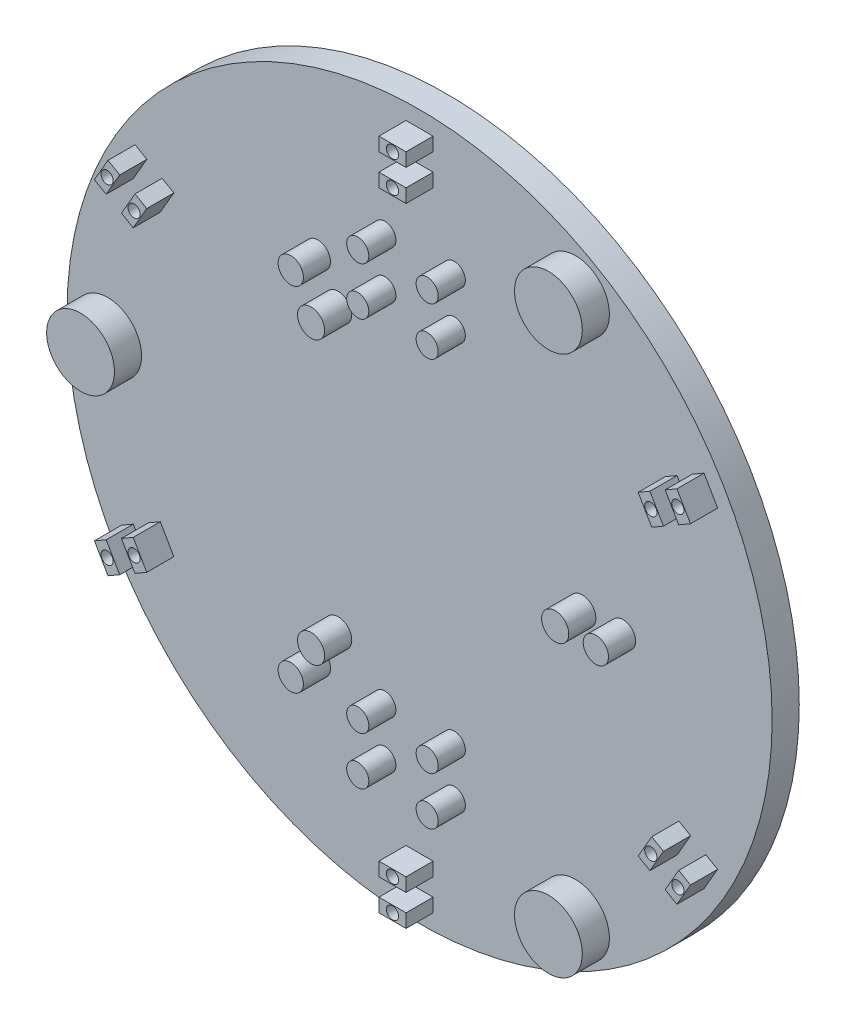
SolidWorks part; units mm, degrees
ref_plane "Front Plane" through (0, 0, 0) normal (0, 0, 1) x (1, 0, 0)
ref_plane "Top Plane" through (0, 0, 0) normal (0, 1, 0) x (1, 0, 0)
ref_plane "Right Plane" through (0, 0, 0) normal (1, 0, 0) x (0, 0, -1)
sketch "Sketch1" plane through (0, 0, 0) normal (0, 0, 1) x (1, 0, 0)
  circle A0 centre (0, 0) radius 33.02
  dimension "D1" = 66.04
extrude "Boss-Extrude1" add sketch "Sketch1" along normal blind 2.54
sketch "Sketch2" plane through (0, 0, 2.54) normal (0, 0, 1) x (1, 0, 0)
  line L0 (0, 33.02) -> (0, 0) construction
  line L1 (0, 0) -> (14.605, 25.2966) construction
  line L2 (14.605, 25.2966) -> (16.51, 28.5962) construction
  circle A1 centre (14.605, 25.2966) radius 3.175
  circle A2 centre (0, 0) radius 33.02 construction
  dimension "D1" = 6.35
  dimension "D2" = 3.81
  dimension "D3" = 30
extrude "Boss-Extrude2" add sketch "Sketch2" along normal blind 2.54
ref_axis "Axis1" through (0, 0, 34.6482) along (0, 0, -1)
pattern_circular "CirPattern1" count 3 over 360 about axis through (0, 0, 34.6482) along (0, 0, -1) of "Boss-Extrude2"
sketch "Sketch3" plane through (0, 0, 2.54) normal (0, 0, 1) x (1, 0, 0)
  line L0 (0, 0) -> (0, -27.94) construction
  line L1 (0, -27.94) -> (0, -33.02) construction
  line L3 (-1.27, -27.305) -> (1.27, -27.305)
  line L4 (-1.27, -27.305) -> (-1.27, -28.575)
  line L5 (-1.27, -28.575) -> (1.27, -28.575)
  line L6 (1.27, -27.305) -> (1.27, -28.575)
  line L7 (-1.27, -27.305) -> (1.27, -28.575) construction
  line L8 (-1.27, -28.575) -> (1.27, -27.305) construction
  line L16 (-1.27, -30.226) -> (1.27, -30.226)
  line L17 (-1.27, -30.226) -> (-1.27, -31.496)
  line L18 (-1.27, -31.496) -> (1.27, -31.496)
  line L19 (1.27, -30.226) -> (1.27, -31.496)
  line L20 (-1.27, -30.226) -> (1.27, -31.496) construction
  line L21 (-1.27, -31.496) -> (1.27, -30.226) construction
  circle A0 centre (0, 0) radius 33.02 construction
  circle A2 centre (0, -27.94) radius 0.5715
  circle A3 centre (0, -30.861) radius 0.5715
  point P10 (-3.81, -30.1721)
  point P11 (0, -30.48)
  point P12 (0, -30.48)
  point P13 (0.0188, -30.5629)
  dimension "D5" = 2.921
  dimension "D4" = 1.143
  dimension "D1" = 2.54
  dimension "D2" = 1.27
  dimension "D3" = 5.08
extrude "Boss-Extrude3" add sketch "Sketch3" along normal blind 2.54
pattern_circular "CirPattern8" count 6 over 360 about axis through (0, 0, 34.6482) along (0, 0, -1) of "Boss-Extrude3"
sketch "Sketch4" plane through (0, 0, 2.54) normal (0, 0, 1) x (1, 0, 0)
  line L0 (0, 0) -> (0, 19.05) construction
  line L1 (0, 0) -> (0, -19.05) construction
  line L2 (-3.2512, 21.2979) -> (3.2512, 21.2979) construction
  line L3 (-3.2512, 21.2979) -> (-3.2512, 16.8021) construction
  line L4 (-3.2512, 16.8021) -> (3.2512, 16.8021) construction
  line L5 (3.2512, 21.2979) -> (3.2512, 16.8021) construction
  line L6 (-3.2512, 21.2979) -> (3.2512, 16.8021) construction
  line L7 (-3.2512, 16.8021) -> (3.2512, 21.2979) construction
  line L9 (-3.2512, -16.8021) -> (3.2512, -16.8021) construction
  line L10 (-3.2512, -16.8021) -> (-3.2512, -21.2979) construction
  line L11 (-3.2512, -21.2979) -> (3.2512, -21.2979) construction
  line L12 (3.2512, -16.8021) -> (3.2512, -21.2979) construction
  line L13 (-3.2512, -16.8021) -> (3.2512, -21.2979) construction
  line L14 (-3.2512, -21.2979) -> (3.2512, -16.8021) construction
  circle A0 centre (-3.2512, 21.2979) radius 1.0363
  circle A1 centre (-3.2512, -16.8021) radius 1.0363
  circle A2 centre (3.2512, 21.2979) radius 1.0363
  circle A3 centre (3.2512, 16.8021) radius 1.0363
  circle A4 centre (-3.2512, 16.8021) radius 1.0363
  circle A5 centre (3.2512, -16.8021) radius 1.0363
  circle A6 centre (3.2512, -21.2979) radius 1.0363
  circle A7 centre (-3.2512, -21.2979) radius 1.0363
  dimension "D4" = 2.0726
  dimension "D1" = 4.4958
  dimension "D2" = 6.5024
  dimension "D3" = 19.05
extrude "Boss-Extrude4" add sketch "Sketch4" along normal blind 2.54
sketch "Sketch5" plane through (0, 0, 2.54) normal (0, 0, 1) x (1, 0, 0)
  line L0 (0, 0) -> (15.24, 0) construction
  line L1 (15.24, 0) -> (19.05, 0) construction
  circle A0 centre (15.24, 0) radius 1.2699
  circle A1 centre (19.05, 0) radius 1.1843
  dimension "D1" = 15.24
  dimension "D2" = 3.81
extrude "Boss-Extrude5" add sketch "Sketch5" along normal blind 2.54
pattern_circular "CirPattern9" count 3 over 360 about axis through (0, 0, 34.6482) along (0, 0, -1) of "Boss-Extrude5"
